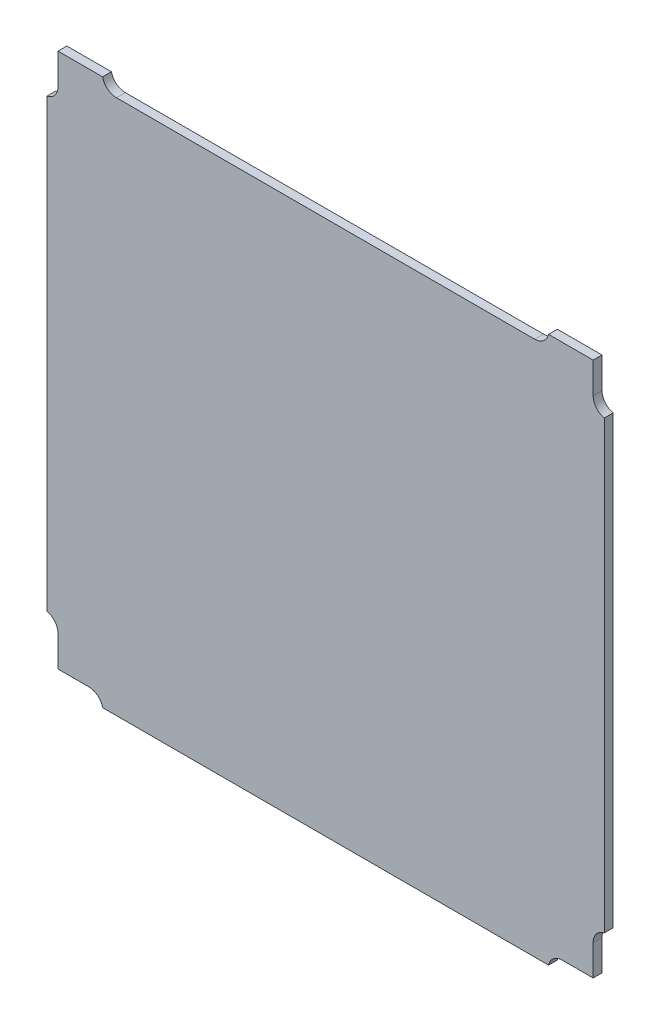
SolidWorks part; units mm, degrees
ref_plane "Front Plane" through (0, 0, 0) normal (0, 0, 1) x (1, 0, 0)
ref_plane "Top Plane" through (0, 0, 0) normal (0, 1, 0) x (1, 0, 0)
ref_plane "Right Plane" through (0, 0, 0) normal (1, 0, 0) x (0, 0, -1)
sketch "Sketch1" plane through (0, 0, 0) normal (0, 0, 1) x (1, 0, 0)
  line L0 (-40, 50) -> (-40, 48)
  line L1 (-50, -50) -> (50, -50)
  line L2 (-50, -50) -> (-50, 50)
  line L3 (-50, 50) -> (50, 50)
  line L4 (50, -50) -> (50, 50)
  line L5 (-50, -50) -> (50, 50) construction
  line L6 (-50, 50) -> (50, -50) construction
  line L7 (-50, 50) -> (-40, 50)
  line L8 (-50, 50) -> (-50, 40)
  line L9 (-40, 48) -> (-48, 48)
  line L10 (-48, 48) -> (-48, 40)
  line L11 (50, 50) -> (40, 50)
  line L12 (50, 50) -> (50, 40)
  line L13 (-48, 40) -> (-50, 40)
  line L14 (50, 40) -> (48, 40)
  line L15 (-50, -50) -> (-37.8649, -50)
  line L16 (-50, -50) -> (-50, -37.8649)
  line L17 (50, 50) -> (50, 40)
  line L18 (50, 50) -> (40, 50)
  line L19 (50, -50) -> (41.5, -50)
  line L20 (50, -50) -> (50, -41.5)
  line L21 (48, 40) -> (48, 48)
  line L22 (48, 48) -> (40, 48)
  line L23 (40, 48) -> (40, 50)
  line L24 (40, -50) -> (40, -48)
  line L25 (50, -50) -> (40, -50)
  line L26 (50, -50) -> (50, -40)
  line L27 (40, -48) -> (48, -48)
  line L28 (48, -48) -> (48, -40)
  line L29 (48, -40) -> (50, -40)
  line L30 (-50, -40) -> (-48, -40)
  line L31 (-50, -50) -> (-50, -40)
  line L32 (-50, -50) -> (-40, -50)
  line L33 (-48, -40) -> (-48, -48)
  line L34 (-48, -48) -> (-40, -48)
  line L35 (-40, -48) -> (-40, -50)
  line L38 (40, 48) -> (40, 46)
  line L39 (40, 46) -> (-40, 46)
  line L40 (-40, 46) -> (-40, 48)
  line L41 (40, 46) -> (-40, 46) construction
  point P0 (0, 0)
  point P38 (0, 0)
  dimension "D1" = 100
  dimension "D2" = 100
  dimension "D3" = 2
  dimension "D4" = 10
  dimension "D6" = 4
  dimension "D5" = 4
extrude "Boss-Extrude1" add sketch "Sketch1" along normal blind 1.5875 contours L1 L4 L3 L2 region at (0, -1.6107, 0)
fillet "Fillet1" radius 2.54 8 edges at (-48, -40, 0.7937) (-40, -48, 0.7937) (40, -48, 0.7937) (48, -40, 0.7937) (48, 40, 0.7937) (-48, 40, 0.7937) (40, 46, 0.7937) (-40, 46, 0.7937)
